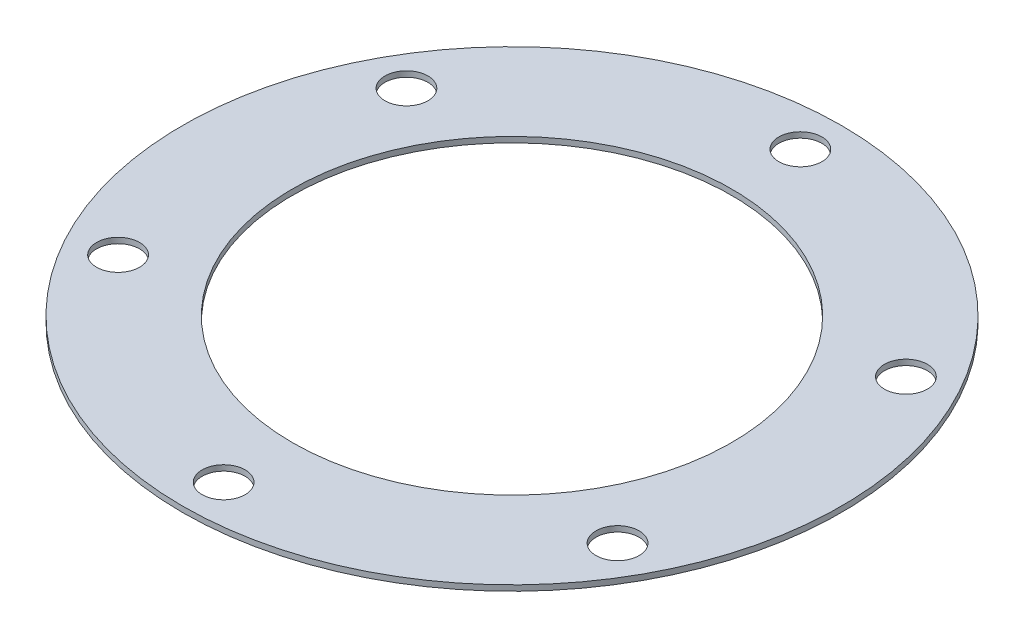
SolidWorks part; units mm, degrees
material "201 Annealed Stainless Steel (SS)"
ref_plane "Front Plane" through (0, 0, 0) normal (0, 0, 1) x (1, 0, 0)
ref_plane "Top Plane" through (0, 0, 0) normal (0, 1, 0) x (1, 0, 0)
ref_plane "Right Plane" through (0, 0, 0) normal (1, 0, 0) x (0, 0, -1)
sketch "Sketch1" plane through (0, 0, 0) normal (0, 1, 0) x (1, 0, 0)
  circle A0 centre (0, 0) radius 50.8
  circle A1 centre (0, 0) radius 33.8636
  circle A2 centre (0, 44.45) radius 3.3147
  circle A3 centre (38.4948, 22.225) radius 3.3147
  circle A4 centre (38.4948, -22.225) radius 3.3147
  circle A5 centre (0, -44.45) radius 3.3147
  circle A6 centre (-38.4948, -22.225) radius 3.3147
  circle A7 centre (-38.4948, 22.225) radius 3.3147
  point P19 (0, 0)
  dimension "D1" = 67.7272
  dimension "D2" = 101.6
  dimension "D3" = 6.6294
  dimension "D4" = 44.45
  dimension "D5" = 6
extrude "Boss-Extrude1" add sketch "Sketch1" along normal blind 0.8636 contours A0 A7 A6 A5 A4 A3 A2 A1 region at (-49.3632, 0, 0)
